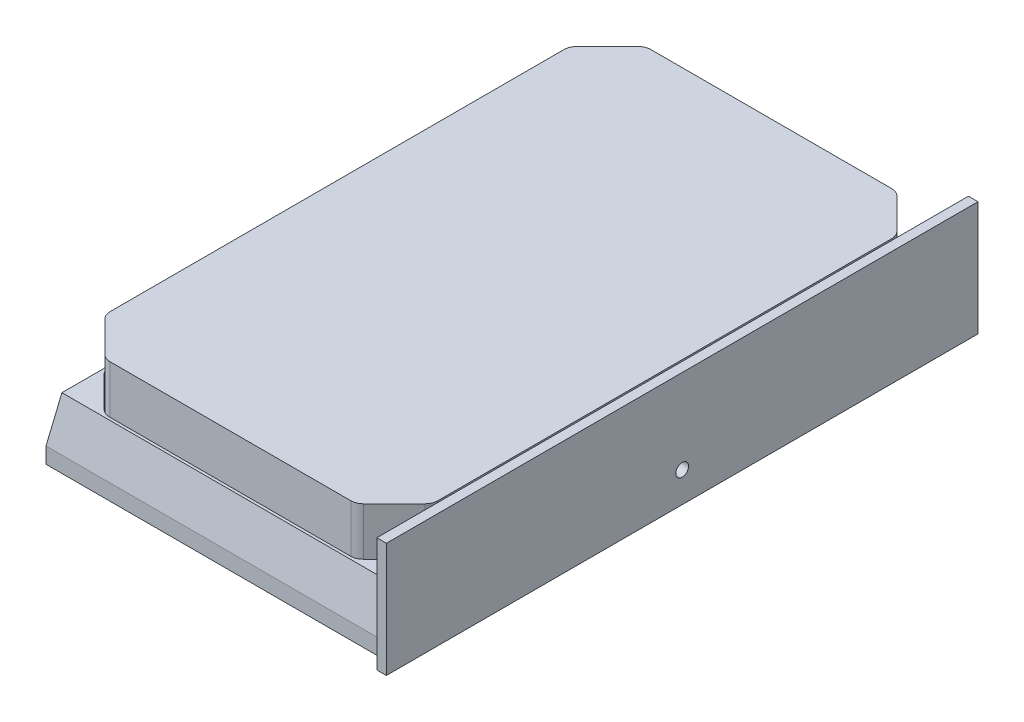
SolidWorks part; units mm, degrees
ref_plane "Front" through (0, 0, 0) normal (0, 0, 1) x (1, 0, 0)
ref_plane "Top" through (0, 0, 0) normal (0, 1, 0) x (1, 0, 0)
ref_plane "Right" through (0, 0, 0) normal (1, 0, 0) x (0, 0, -1)
sketch "Sketch1" plane through (0, 0, 0) normal (0, 1, 0) x (1, 0, 0)
  line L1 (-51.5, 85) -> (51.5, 85)
  line L2 (-51.5, 85) -> (-51.5, -85)
  line L3 (-51.5, -85) -> (51.5, -85)
  line L4 (51.5, 85) -> (51.5, -85)
  line L5 (0, -85) -> (0, 85) construction
  line L6 (-51.5, 0) -> (51.5, 0) construction
  point P0 (0, 0)
  dimension "D1" = 103
  dimension "D2" = 170
extrude "Boss-Extrude1" add sketch "Sketch1" along normal blind 30
chamfer "Chamfer1" distance 12 angle 45 4 edges at (51.5, 15, -85) (-51.5, 15, -85) (-51.5, 15, 85) (51.5, 15, 85)
fillet "Fillet1" radius 4 8 edges at (-51.5, 15, 73) (-39.5, 15, 85) (39.5, 15, 85) (51.5, 15, 73) (51.5, 15, -73) (39.5, 15, -85) (-51.5, 15, -73) (-39.5, 15, -85)
sketch "Sketch2" plane through (0, 0, 0) normal (0, 1, 0) x (1, 0, 0)
  line L9 (-54, 89) -> (54, 89)
  line L10 (-54, 89) -> (-54, -89)
  line L11 (-54, -89) -> (54, -89)
  line L12 (54, 89) -> (54, -89)
  line L13 (0, -89) -> (0, 89) construction
  line L14 (-54, 0) -> (54, 0) construction
  line L16 (-51.65, 71.3431) -> (-51.65, -71.3431)
  line L17 (-50.4345, -74.2776) -> (-40.7776, -83.9345)
  line L18 (-37.8431, -85.15) -> (37.8431, -85.15)
  line L19 (40.7776, -83.9345) -> (50.4345, -74.2776)
  line L20 (51.65, -71.3431) -> (51.65, 71.3431)
  line L21 (50.4345, 74.2776) -> (40.7776, 83.9345)
  line L22 (37.8431, 85.15) -> (-37.8431, 85.15)
  line L23 (-40.7776, 83.9345) -> (-50.4345, 74.2776)
  line L24 (-51.65, 71.3431) -> (-51.65, -71.3431)
  line L25 (-50.4345, -74.2776) -> (-40.7776, -83.9345)
  line L26 (-37.8431, -85.15) -> (37.8431, -85.15)
  line L27 (40.7776, -83.9345) -> (50.4345, -74.2776)
  line L28 (51.65, -71.3431) -> (51.65, 71.3431)
  line L29 (50.4345, 74.2776) -> (40.7776, 83.9345)
  line L30 (37.8431, 85.15) -> (-37.8431, 85.15)
  line L31 (-40.7776, 83.9345) -> (-50.4345, 74.2776)
  arc A16 (-51.65, -71.3431) -> (-50.4345, -74.2776) centre (-47.5, -71.3431) ccw
  arc A17 (-40.7776, -83.9345) -> (-37.8431, -85.15) centre (-37.8431, -81) ccw
  arc A18 (37.8431, -85.15) -> (40.7776, -83.9345) centre (37.8431, -81) ccw
  arc A19 (50.4345, -74.2776) -> (51.65, -71.3431) centre (47.5, -71.3431) ccw
  arc A20 (51.65, 71.3431) -> (50.4345, 74.2776) centre (47.5, 71.3431) ccw
  arc A21 (40.7776, 83.9345) -> (37.8431, 85.15) centre (37.8431, 81) ccw
  arc A22 (-37.8431, 85.15) -> (-40.7776, 83.9345) centre (-37.8431, 81) ccw
  arc A23 (-50.4345, 74.2776) -> (-51.65, 71.3431) centre (-47.5, 71.3431) ccw
  arc A24 (-51.65, -71.3431) -> (-50.4345, -74.2776) centre (-47.5, -71.3431) ccw
  arc A25 (-40.7776, -83.9345) -> (-37.8431, -85.15) centre (-37.8431, -81) ccw
  arc A26 (37.8431, -85.15) -> (40.7776, -83.9345) centre (37.8431, -81) ccw
  arc A27 (50.4345, -74.2776) -> (51.65, -71.3431) centre (47.5, -71.3431) ccw
  arc A28 (51.65, 71.3431) -> (50.4345, 74.2776) centre (47.5, 71.3431) ccw
  arc A29 (40.7776, 83.9345) -> (37.8431, 85.15) centre (37.8431, 81) ccw
  arc A30 (-37.8431, 85.15) -> (-40.7776, 83.9345) centre (-37.8431, 81) ccw
  arc A31 (-50.4345, 74.2776) -> (-51.65, 71.3431) centre (-47.5, 71.3431) ccw
  point P0 (0, 0)
  dimension "D2" = 108
  dimension "D3" = 178
  dimension "D1" = 0.15
extrude "Boss-Extrude2" add sketch "Sketch2" along normal blind 15 separate body
sketch "Sketch3" plane through (0, 0, 0) normal (0, -1, 0) x (1, 0, 0)
  line L4 (54, -89) -> (54, 89)
  line L5 (54, 89) -> (-54, 89)
  line L6 (-54, 89) -> (-54, -89)
  line L7 (-54, -89) -> (54, -89)
  line L8 (54, -89) -> (54, 89)
  line L9 (54, 89) -> (-54, 89)
  line L10 (-54, 89) -> (-54, -89)
  line L11 (-54, -89) -> (54, -89)
  dimension "D1" = 0
extrude "Boss-Extrude3" add sketch "Sketch3" along normal blind 4
chamfer "Chamfer2" distance 14 distance2 3 2 edges at (0, 15, -89) (0, 15, 89) first distance on face at (0, 5.5, -89) first distance on face at (0, 5.5, 89)
chamfer "Chamfer3" distance 14 distance2 2 1 edges at (-54, 15, 0) first distance on face at (-54, 4, 0)
sketch "Sketch6" plane through (54, 0, 0) normal (1, 0, 0) x (0, 0, -1)
  line L0 (0, 0) -> (0, -4) construction
  line L1 (-93, -4) -> (93, -4)
  line L2 (-93, -4) -> (-93, 32)
  line L3 (-93, 32) -> (93, 32)
  line L4 (93, -4) -> (93, 32)
  line L5 (89, -4) -> (-89, -4) construction
  dimension "D1" = 186
  dimension "D2" = 36
extrude "Boss-Extrude4" add sketch "Sketch6" along normal blind 3
sketch "Sketch7" plane through (57, 0, 0) normal (1, 0, 0) x (0, 0, -1)
  line L0 (0, 15) -> (0, -4) construction
  line L1 (-86, 15) -> (86, 15) construction
  line L2 (-93, -4) -> (93, -4) construction
  circle A0 centre (0, 5.5) radius 2
  point P8 (0, 5.5)
  dimension "D1" = 4
extrude "Cut-Extrude1" cut sketch "Sketch7" against normal blind 6
chamfer "Chamfer4" distance 14 distance2 3 1 edges at (54, 15, 0) first distance on face at (54, 8, 0)
